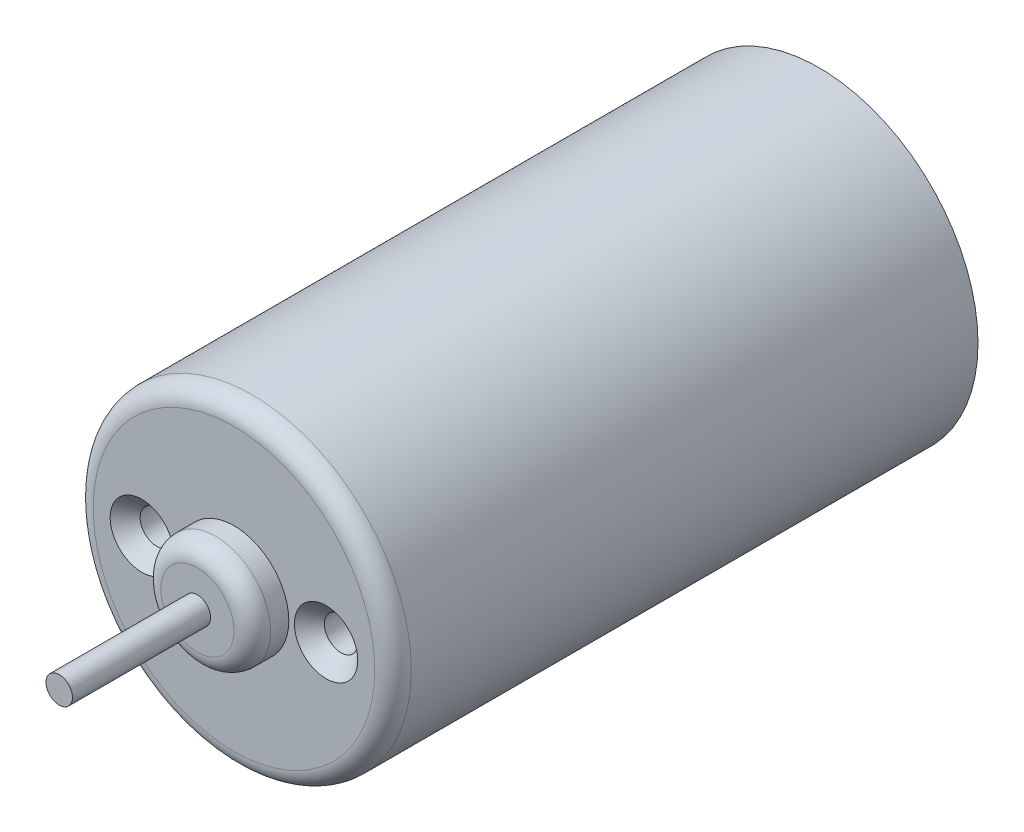
SolidWorks part; units mm, degrees
ref_plane "Front Plane" through (0, 0, 0) normal (0, 0, 1) x (1, 0, 0)
ref_plane "Top Plane" through (0, 0, 0) normal (0, 1, 0) x (1, 0, 0)
ref_plane "Right Plane" through (0, 0, 0) normal (1, 0, 0) x (0, 0, -1)
sketch "Sketch1" plane through (0, 0, 0) normal (0, 0, 1) x (1, 0, 0)
  circle A0 centre (0, 0) radius 13.8112
  dimension "D1" = 27.6225
extrude "Boss-Extrude1" add sketch "Sketch1" along normal blind 50.8
fillet "Fillet1" radius 1.5875 1 edges at (13.8112, 0, 50.8)
sketch "Sketch2" plane through (0, 0, 50.8) normal (0, 0, 1) x (1, 0, 0)
  circle A0 centre (0, 0) radius 4.7625
  dimension "D1" = 9.525
extrude "Boss-Extrude2" add sketch "Sketch2" along normal blind 3.175
fillet "Fillet2" radius 1.5875 1 edges at (4.7625, 0, 53.975)
hole_wizard "CSK for M2.5 Flat Head Machine Screw1" positions "Sketch3" profile "Sketch4" countersink size "M2.5" standard "ANSI Metric"
sketch "Sketch3" plane through (0, 0, 50.8) normal (0, 0, 1) x (1, 0, 0)
  point P0 (-8.001, 0)
  point P2 (8.001, 0)
  point P6 (0, 0)
  point P7 (0, 0)
  dimension "D1" = 16.002
  dimension "D2" = 8.001
sketch "Sketch4" plane through (-8.001, 0, 50.8) normal (1, 0, 0) x (0, -1, 0)
  line L0 (0, 0) -> (0, 13.5712)
  line L1 (0, 13.5712) -> (1.45, 12.7)
  line L2 (1.45, 12.7) -> (1.45, 1.3)
  line L3 (1.45, 1.3) -> (2.75, 0)
  line L5 (2.75, 0) -> (0, 0)
  line L6 (-1.45, 1.3) -> (-2.75, 0) construction
  line L10 (0, 13.5712) -> (-1.45, 12.7) construction
  line L11 (0, -6.35) -> (0, 107.95) construction
  dimension "Hole Dia." = 2.9
  dimension "Hole Depth" = 12.7
  dimension "Near C'Sink Dia." = 5.5
  dimension "Near C'Sink Angle" = 90
  dimension "Drill Angle" = 118
sketch "Sketch5" plane through (0, 0, 53.975) normal (0, 0, 1) x (1, 0, 0)
  circle A0 centre (0, 0) radius 1.15
  dimension "D1" = 2.3
extrude "Boss-Extrude3" add sketch "Sketch5" along normal blind 12
